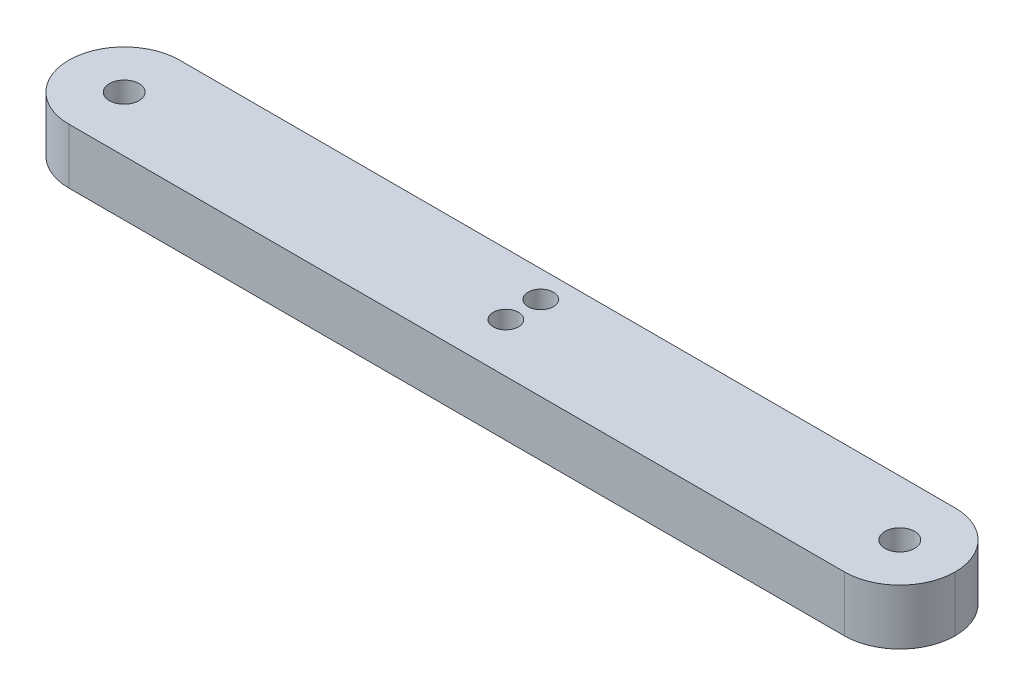
SolidWorks part; units mm, degrees
ref_plane "Front Plane" through (0, 0, 0) normal (0, 0, 1) x (1, 0, 0)
ref_plane "Top Plane" through (0, 0, 0) normal (0, 1, 0) x (1, 0, 0)
ref_plane "Right Plane" through (0, 0, 0) normal (1, 0, 0) x (0, 0, -1)
sketch "Sketch1" plane through (0, 0, 0) normal (0, 1, 0) x (1, 0, 0)
  line L0 (-44.45, 0) -> (0, 0) construction
  line L1 (-50.8, -6.35) -> (50.8, -6.35) construction
  line L2 (-50.8, -6.35) -> (-50.8, 6.35)
  line L3 (-50.8, 6.35) -> (50.8, 6.35)
  line L4 (50.8, -6.35) -> (50.8, 6.35)
  line L5 (-50.8, -6.35) -> (50.8, 6.35) construction
  line L6 (-50.8, 6.35) -> (50.8, -6.35) construction
  line L7 (0, 6.35) -> (0, -6.35) construction
  line L8 (-6.35, -31.75) -> (-6.35, 6.35) construction
  line L9 (-6.35, -31.75) -> (6.35, -31.75)
  line L10 (-6.35, 6.35) -> (6.35, 6.35)
  line L11 (6.35, -31.75) -> (6.35, 6.35) construction
  line L12 (-6.35, -31.75) -> (6.35, 6.35) construction
  line L13 (-6.35, 6.35) -> (6.35, -31.75) construction
  line L14 (-50.8, -6.35) -> (-6.35, -6.35)
  line L15 (-6.35, -6.35) -> (-6.35, -31.75)
  line L16 (6.35, -31.75) -> (6.35, -6.35)
  line L17 (6.35, -6.35) -> (50.8, -6.35)
  line L18 (-6.35, -6.35) -> (6.35, -6.35)
  circle A0 centre (-44.45, 0) radius 1.7
  circle A1 centre (44.45, 0) radius 1.7
  circle A2 centre (0, -25.4) radius 1.7
  point P0 (0, 0)
  point P13 (0, -12.7)
  point P22 (0, -31.75)
  dimension "D5" = 12.7
  dimension "D6" = 38.1
  dimension "D3" = 6.35
  dimension "D4" = 3.4
  dimension "D7" = 6.35
  dimension "D1" = 101.6
  dimension "D2" = 12.7
extrude "Boss-Extrude1" add sketch "Sketch1" along normal blind 6.35 contours L16 L17 L4 L3 L2 L14 L15 L9 A2 A0 A1 region at (0, 0, 0)
fillet "Fillet1" radius 6.35 4 edges at (50.8, 3.175, -6.35) (-50.8, 3.175, -6.35) (-50.8, 3.175, 6.35) (50.8, 3.175, 6.35)
sketch "Sketch2" plane through (0, 6.35, 0) normal (0, 1, 0) x (1, 0, 0)
  line L0 (-20.5, 10.2) -> (10, 10.2) construction
  line L1 (20.5, -10.2) -> (-20.5, -10.2) construction
  line L2 (20.5, -10.2) -> (20.5, 10.2) construction
  line L3 (20.5, 10.2) -> (-20.5, 10.2) construction
  line L4 (-20.5, -10.2) -> (-20.5, 10.2) construction
  line L5 (20.5, -10.2) -> (-20.5, 10.2) construction
  line L6 (20.5, 10.2) -> (-20.5, -10.2) construction
  line L7 (10, 10.2) -> (10, -10.2) construction
  point P0 (0, 0)
  dimension "D1" = 41
  dimension "D2" = 20.4
  dimension "D3" = 30.5
sketch "Sketch3" plane through (0, 6.35, 0) normal (0, 1, 0) x (1, 0, 0)
  line L0 (0, 14.1517) -> (0, -11.6855) construction
  circle A0 centre (0, -0.7045) radius 1.45
  circle A1 centre (0, 3.2955) radius 1.45
  point P7 (0, 3.2955)
  dimension "D1" = 4
  dimension "D2" = 2.9
  dimension "D3" = 2.9
extrude "Cut-Extrude1" cut sketch "Sketch3" against normal through all both and the other way through all
